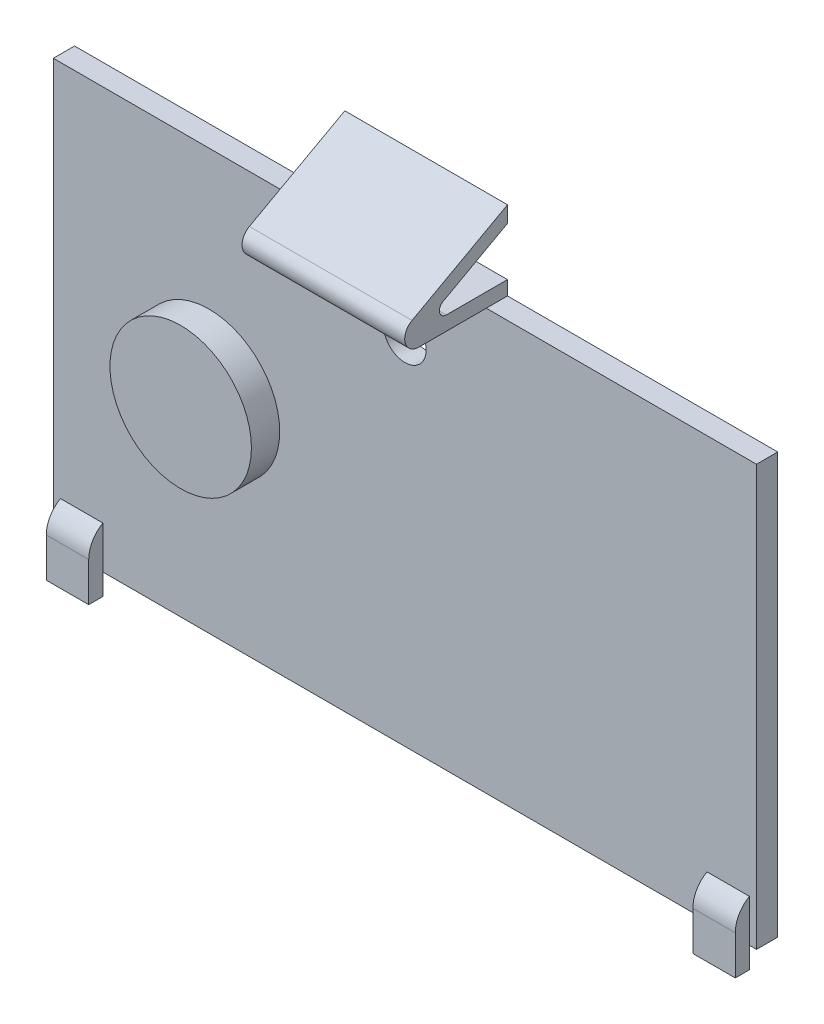
SolidWorks part; units mm, degrees
ref_plane "Alzado" through (0, 0, 0) normal (0, 0, 1) x (1, 0, 0)
ref_plane "Planta" through (0, 0, 0) normal (0, 1, 0) x (1, 0, 0)
ref_plane "Vista lateral" through (0, 0, 0) normal (1, 0, 0) x (0, 0, -1)
sketch "Croquis1" plane through (0, 0, 0) normal (0, 0, 1) x (1, 0, 0)
  line L1 (-24.85, 29.7) -> (24.85, 29.7)
  line L2 (-24.85, 29.7) -> (-24.85, 0)
  line L3 (-24.85, 0) -> (24.85, 0)
  line L4 (24.85, 29.7) -> (24.85, 0)
  dimension "D1" = 49.7
  dimension "D2" = 29.7
extrude "Saliente-Extruir1" add sketch "Croquis1" along normal blind 1.5
sketch "Croquis2" plane through (0, 0, 1.5) normal (0, 0, 1) x (1, 0, 0)
  line L0 (-24.85, 29.7) -> (-24.85, 0) construction
  circle A0 centre (-13.85, 14.85) radius 5
  point P4 (0, 0)
  dimension "D1" = 10
  dimension "D2" = 11
extrude "Saliente-Extruir2" add sketch "Croquis2" along normal blind 2
sketch "Croquis3" plane through (0, 0, 1.5) normal (0, 0, 1) x (1, 0, 0)
  line L0 (-24.85, 0) -> (24.85, 0) construction
  line L1 (-24.35, 0) -> (-21.35, 0)
  line L2 (-24.35, 0) -> (-24.35, 3)
  line L3 (-24.35, 3) -> (-21.35, 3)
  line L4 (-21.35, 0) -> (-21.35, 3)
  line L5 (-24.85, 29.7) -> (-24.85, 0) construction
  line L6 (21.35, 0) -> (24.35, 0)
  line L7 (21.35, 0) -> (21.35, 3)
  line L8 (21.35, 3) -> (24.35, 3)
  line L9 (24.35, 0) -> (24.35, 3)
  line L10 (24.85, 0) -> (24.85, 29.7) construction
  dimension "D1" = 3
  dimension "D2" = 3
  dimension "D3" = 3
  dimension "D4" = 3
  dimension "D5" = 0.5
  dimension "D6" = 0.5
extrude "Saliente-Extruir3" add sketch "Croquis3" along normal blind 1
sketch "Croquis4" plane through (0, 0, 0) normal (0, -1, 0) x (1, 0, 0)
  line L1 (-24.35, 2.5) -> (-21.35, 2.5)
  line L2 (-24.35, 2.5) -> (-24.35, 1.5)
  line L3 (-24.35, 1.5) -> (-21.35, 1.5)
  line L4 (-21.35, 2.5) -> (-21.35, 1.5)
  line L5 (24.35, 2.5) -> (24.35, 1.5) construction
  line L6 (21.35, 2.5) -> (24.35, 2.5)
  line L7 (21.35, 2.5) -> (21.35, 1.5)
  line L8 (21.35, 1.5) -> (24.35, 1.5)
  line L9 (24.35, 2.5) -> (24.35, 1.5)
  dimension "D1" = 1
  dimension "D2" = 1
extrude "Saliente-Extruir4" add sketch "Croquis4" along normal blind 1.5
fillet "Redondeo1" radius 2 2 edges at (-22.85, 3, 2.5) (22.85, 3, 2.5)
sketch "Croquis6" plane through (0, 0, 0) normal (1, 0, 0) x (0, 0, -1)
  line L12 (0, 29.7) -> (-6.2654, 29.7)
  line L13 (-6.7468, 31.5765) -> (0, 35.2826)
  line L14 (0, 35.2826) -> (0, 34.1417)
  line L15 (0, 34.1417) -> (-4.5574, 31.6382)
  line L16 (-4.3167, 30.7) -> (0, 30.7)
  line L17 (0, 30.7) -> (0, 29.7)
  arc A0 (-6.7468, 31.5765) -> (-6.2654, 29.7) centre (-6.2654, 30.7) ccw
  arc A1 (-4.3167, 30.7) -> (-4.5574, 31.6382) centre (-4.3167, 31.2) cw
  dimension "D3" = 1
  dimension "D4" = 0.5
  dimension "D1" = 1
  dimension "D2" = 1
extrude "Saliente-Extruir5" add sketch "Croquis6" along normal mid plane 11.5
sketch "Croquis7" plane through (0, 0, 0) normal (0, 0, -1) x (-1, 0, 0)
  line L0 (24.85, 0) -> (-24.85, 0) construction
  circle A0 centre (0, 25) radius 1.5
  point P6 (0, 0)
  dimension "D1" = 3
  dimension "D2" = 25
extrude "Cortar-Extruir1" cut sketch "Croquis7" against normal blind 11.5
